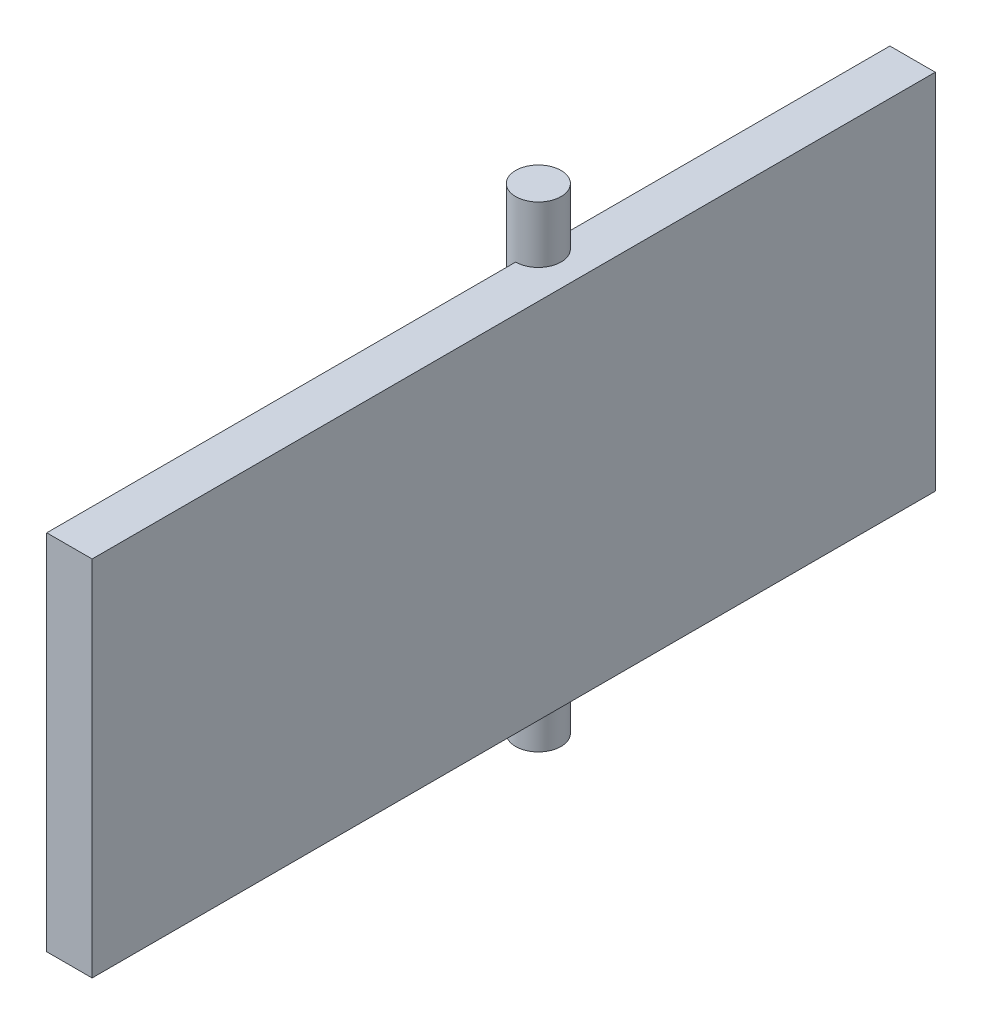
SolidWorks part; units mm, degrees
ref_plane "Front Plane" through (0, 0, 0) normal (0, 0, 1) x (1, 0, 0)
ref_plane "Top Plane" through (0, 0, 0) normal (0, 1, 0) x (1, 0, 0)
ref_plane "Right Plane" through (0, 0, 0) normal (1, 0, 0) x (0, 0, -1)
sketch "Sketch1" plane through (14.295, 0, 0) normal (1, 0, 0) x (0, 0, -1)
  line L0 (-37.175, 55.692) -> (-37.175, 57.192) construction
  line L1 (-37.175, 73.692) -> (0, 73.692)
  line L2 (-37.175, 73.692) -> (-37.175, 57.692)
  line L3 (-37.175, 57.692) -> (0, 57.692)
  line L4 (0, 73.692) -> (0, 57.692)
  line L5 (-34.175, 75.692) -> (-30.175, 75.692) construction
  line L6 (-37.175, 55.692) -> (-23, 55.692) construction
  line L8 (-18, 75.692) -> (-18, 55.692) construction
  dimension "D1" = 2
  dimension "D2" = 2
  dimension "D3" = 18
extrude "Boss-Extrude1" add sketch "Sketch1" along normal blind 2
sketch "Sketch2" plane through (0, 73.692, 0) normal (0, 1, 0) x (1, 0, 0)
  circle A0 centre (14.295, -15.5) radius 1
  dimension "D1" = 2
extrude "Boss-Extrude2" add sketch "Sketch2" along normal mid plane 5
ref_plane "Plane1" through (0, 65.692, 0) normal (0, 1, 0) x (1, 0, 0)
mirror "Mirror1" about plane through (0, 65.692, 0) normal (0, 1, 0) of "Boss-Extrude2"
fillet "Fillet1" radius 1 2 edges at (14.295, 71.192, 15.5) (14.295, 60.192, 15.5)
